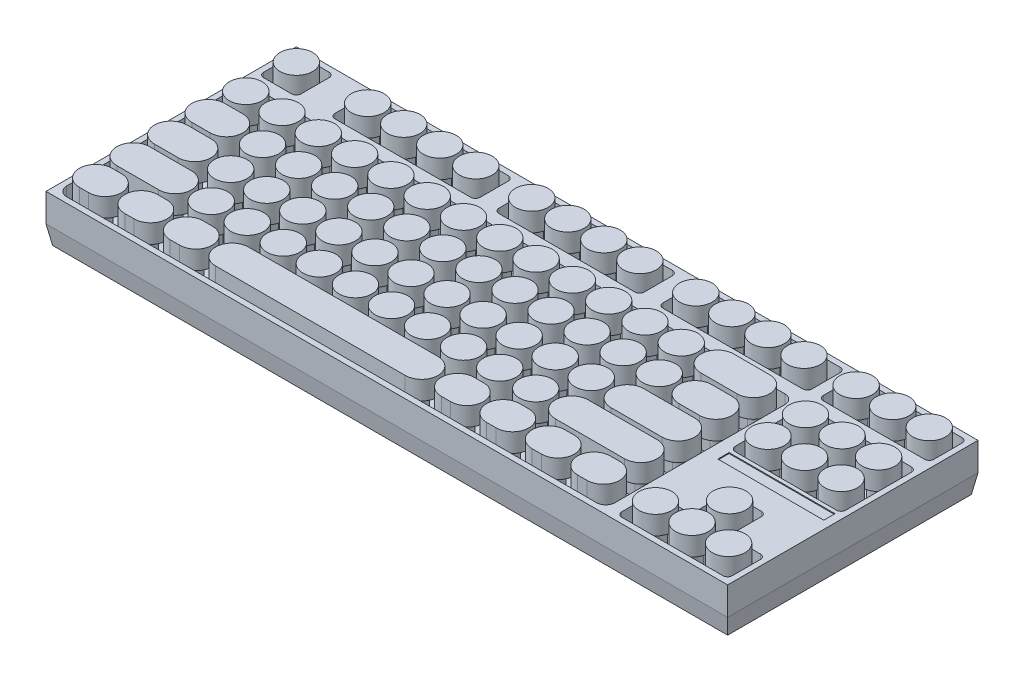
SolidWorks part; units mm, degrees
ref_plane "Front Plane" through (0, 0, 0) normal (0, 0, 1) x (1, 0, 0)
ref_plane "Top Plane" through (0, 0, 0) normal (0, 1, 0) x (1, 0, 0)
ref_plane "Right Plane" through (0, 0, 0) normal (1, 0, 0) x (0, 0, -1)
sketch "Sketch1" plane through (0, 0, 0) normal (0, 1, 0) x (1, 0, 0)
  line L1 (180, 65) -> (-180, 65)
  line L2 (180, 65) -> (180, -65)
  line L3 (180, -65) -> (-180, -65)
  line L4 (-180, 65) -> (-180, -65)
  line L5 (180, 65) -> (-180, -65) construction
  line L6 (180, -65) -> (-180, 65) construction
  point P0 (0, 0)
  dimension "D1" = 360
  dimension "D2" = 130
extrude "Boss-Extrude1" add sketch "Sketch1" along normal blind 10
draft "Draft1" type of draft neutral plane draft angle 10 faces to draft 4 face at (180, 5, 0) face at (0, 5, -65) face at (-180, 5, 0) face at (0, 5, 65) neutral plane through (0, 0, 0) neutral plane normal (0, -1, 0) parameters "D1"=10
sketch "Sketch2" plane through (0, 10, 0) normal (0, 1, 0) x (1, 0, 0)
  line L0 (111.2633, 63.7633) -> (36.7667, 63.7633)
  line L1 (113.7633, 61.2633) -> (113.7633, 46.2633)
  line L2 (111.2633, 43.7633) -> (36.7667, 43.7633)
  line L3 (34.2667, 61.2633) -> (34.2667, 46.2633)
  line L4 (176.2633, 63.7633) -> (122.2633, 63.7633)
  line L5 (176.2633, -43.7633) -> (122.2633, -43.7633) construction
  line L6 (178.7633, -46.2633) -> (178.7633, -61.2633)
  line L7 (176.2633, -63.7633) -> (122.2633, -63.7633)
  line L8 (119.7633, -46.2633) -> (119.7633, -61.2633)
  line L9 (178.7633, -43.7633) -> (119.7633, -63.7633) construction
  line L10 (178.7633, -63.7633) -> (119.7633, -43.7633) construction
  line L11 (156.7633, -23.7633) -> (141.7633, -23.7633)
  line L12 (159.2633, -26.2633) -> (159.2633, -41.2633)
  line L13 (159.2633, -43.7633) -> (139.2633, -43.7633) construction
  line L14 (139.2633, -26.2633) -> (139.2633, -41.2633)
  line L15 (159.2633, -23.7633) -> (139.2633, -43.7633) construction
  line L16 (-178.7633, 66.7633) -> (-178.7633, -66.7633)
  line L17 (-178.7633, 31.7633) -> (-178.7633, -58.7633)
  line L18 (159.2633, -43.7633) -> (139.2633, -23.7633) construction
  line L19 (181.7633, 36.7633) -> (-181.7633, 36.7633)
  line L20 (108.7633, 36.7633) -> (-173.7633, 36.7633)
  line L21 (178.7633, 61.2633) -> (178.7633, 46.2633)
  line L22 (113.7633, -66.7633) -> (113.7633, 66.7633)
  line L23 (113.7633, -58.7633) -> (113.7633, 31.7633)
  line L24 (176.2633, 43.7633) -> (122.2633, 43.7633)
  line L25 (-181.7633, -63.7633) -> (181.7633, -63.7633)
  line L26 (-173.7633, -63.7633) -> (108.7633, -63.7633)
  line L27 (-181.7633, 66.7633) -> (-181.7633, -66.7633) construction
  line L28 (-161.2633, 63.7633) -> (-176.2633, 63.7633)
  line L29 (-158.7633, 61.2633) -> (-158.7633, 46.2633)
  line L30 (-161.2633, 43.7633) -> (-176.2633, 43.7633)
  line L31 (-178.7633, 61.2633) -> (-178.7633, 46.2633)
  line L32 (-158.7633, 63.7633) -> (-178.7633, 43.7633) construction
  line L33 (-158.7633, 43.7633) -> (-178.7633, 63.7633) construction
  line L34 (181.7633, 66.7633) -> (-181.7633, 66.7633) construction
  line L35 (-181.7633, -66.7633) -> (181.7633, -66.7633) construction
  line L36 (-65.7333, 63.7633) -> (-138.2333, 63.7633)
  line L37 (-63.2333, 61.2633) -> (-63.2333, 46.2633)
  line L38 (-65.7333, 43.7633) -> (-138.2333, 43.7633)
  line L39 (-140.7333, 61.2633) -> (-140.7333, 46.2633)
  line L40 (-63.2333, 63.7633) -> (-140.7333, 43.7633) construction
  line L41 (-63.2333, 43.7633) -> (-140.7333, 63.7633) construction
  line L42 (181.7633, -66.7633) -> (181.7633, 66.7633) construction
  line L43 (-181.7633, 66.7633) -> (-181.7633, -66.7633)
  line L44 (-181.7633, -66.7633) -> (181.7633, -66.7633)
  line L45 (181.7633, -66.7633) -> (181.7633, 66.7633)
  line L46 (181.7633, 66.7633) -> (-181.7633, 66.7633)
  line L47 (21.7667, 63.7633) -> (-50.7333, 63.7633)
  line L48 (24.2667, 61.2633) -> (24.2667, 46.2633)
  line L49 (21.7667, 43.7633) -> (-50.7333, 43.7633)
  line L50 (-53.2333, 61.2633) -> (-53.2333, 46.2633)
  line L51 (119.7633, 61.2633) -> (119.7633, 46.2633)
  line L52 (122.2633, -43.7633) -> (136.7633, -43.7633)
  line L53 (176.2633, 36.7633) -> (122.2633, 36.7633)
  line L54 (178.7633, 34.2633) -> (178.7633, -0.7367)
  line L55 (176.2633, -3.2367) -> (122.2633, -3.2367)
  line L56 (119.7633, 34.2633) -> (119.7633, -0.7367)
  line L57 (178.7633, 36.7633) -> (119.7633, -3.2367) construction
  line L58 (178.7633, -3.2367) -> (119.7633, 36.7633) construction
  line L59 (176.2633, -43.7633) -> (161.7633, -43.7633)
  arc A0 (108.7633, -63.7633) -> (113.7633, -58.7633) centre (108.7633, -58.7633) ccw
  arc A1 (113.7633, 31.7633) -> (108.7633, 36.7633) centre (108.7633, 31.7633) ccw
  arc A2 (-173.7633, -63.7633) -> (-178.7633, -58.7633) centre (-173.7633, -58.7633) cw
  arc A3 (-178.7633, 31.7633) -> (-173.7633, 36.7633) centre (-173.7633, 31.7633) cw
  arc A4 (178.7633, -61.2633) -> (176.2633, -63.7633) centre (176.2633, -61.2633) cw
  arc A5 (176.2633, -43.7633) -> (178.7633, -46.2633) centre (176.2633, -46.2633) cw
  arc A6 (122.2633, -43.7633) -> (119.7633, -46.2633) centre (122.2633, -46.2633) ccw
  arc A7 (122.2633, -63.7633) -> (119.7633, -61.2633) centre (122.2633, -61.2633) cw
  arc A8 (156.7633, -23.7633) -> (159.2633, -26.2633) centre (156.7633, -26.2633) cw
  arc A9 (141.7633, -23.7633) -> (139.2633, -26.2633) centre (141.7633, -26.2633) ccw
  arc A10 (178.7633, -0.7367) -> (176.2633, -3.2367) centre (176.2633, -0.7367) cw
  arc A11 (122.2633, -3.2367) -> (119.7633, -0.7367) centre (122.2633, -0.7367) cw
  arc A12 (122.2633, 36.7633) -> (119.7633, 34.2633) centre (122.2633, 34.2633) ccw
  arc A13 (176.2633, 36.7633) -> (178.7633, 34.2633) centre (176.2633, 34.2633) cw
  arc A14 (178.7633, 46.2633) -> (176.2633, 43.7633) centre (176.2633, 46.2633) cw
  arc A15 (176.2633, 63.7633) -> (178.7633, 61.2633) centre (176.2633, 61.2633) cw
  arc A16 (122.2633, 63.7633) -> (119.7633, 61.2633) centre (122.2633, 61.2633) ccw
  arc A17 (122.2633, 43.7633) -> (119.7633, 46.2633) centre (122.2633, 46.2633) cw
  arc A18 (113.7633, 46.2633) -> (111.2633, 43.7633) centre (111.2633, 46.2633) cw
  arc A19 (111.2633, 63.7633) -> (113.7633, 61.2633) centre (111.2633, 61.2633) cw
  arc A20 (36.7667, 63.7633) -> (34.2667, 61.2633) centre (36.7667, 61.2633) ccw
  arc A21 (36.7667, 43.7633) -> (34.2667, 46.2633) centre (36.7667, 46.2633) cw
  arc A22 (24.2667, 46.2633) -> (21.7667, 43.7633) centre (21.7667, 46.2633) cw
  arc A23 (21.7667, 63.7633) -> (24.2667, 61.2633) centre (21.7667, 61.2633) cw
  arc A24 (-50.7333, 43.7633) -> (-53.2333, 46.2633) centre (-50.7333, 46.2633) cw
  arc A25 (-50.7333, 63.7633) -> (-53.2333, 61.2633) centre (-50.7333, 61.2633) ccw
  arc A26 (-63.2333, 46.2633) -> (-65.7333, 43.7633) centre (-65.7333, 46.2633) cw
  arc A27 (-65.7333, 63.7633) -> (-63.2333, 61.2633) centre (-65.7333, 61.2633) cw
  arc A28 (-138.2333, 43.7633) -> (-140.7333, 46.2633) centre (-138.2333, 46.2633) cw
  arc A29 (-138.2333, 63.7633) -> (-140.7333, 61.2633) centre (-138.2333, 61.2633) ccw
  arc A30 (-158.7633, 46.2633) -> (-161.2633, 43.7633) centre (-161.2633, 46.2633) cw
  arc A31 (-176.2633, 43.7633) -> (-178.7633, 46.2633) centre (-176.2633, 46.2633) cw
  arc A32 (-176.2633, 63.7633) -> (-178.7633, 61.2633) centre (-176.2633, 61.2633) ccw
  arc A33 (-161.2633, 63.7633) -> (-158.7633, 61.2633) centre (-161.2633, 61.2633) cw
  arc A34 (136.7633, -43.7633) -> (139.2633, -41.2633) centre (136.7633, -41.2633) ccw
  arc A35 (159.2633, -41.2633) -> (161.7633, -43.7633) centre (161.7633, -41.2633) ccw
  point P22 (-168.7633, 53.7633)
  point P30 (-101.9833, 53.7633)
  point P42 (149.2633, -53.7633)
  point P47 (149.2633, -33.7633)
  point P57 (149.2633, 16.7633)
  point P94 (178.7633, 43.7633)
  point P97 (178.7633, 63.7633)
  point P104 (113.7633, 43.7633)
  point P107 (113.7633, 63.7633)
  point P110 (34.2667, 63.7633)
  point P115 (24.2667, 43.7633)
  point P118 (24.2667, 63.7633)
  point P123 (-53.2333, 63.7633)
  point P153 (0, 0)
  dimension "D5" = 5
  dimension "D34" = 2.5
  dimension "D35" = 2.5
  dimension "D6" = 20
  dimension "D7" = 3
  dimension "D8" = 3
  dimension "D9" = 18.03
  dimension "D10" = 77.5
  dimension "D11" = 20
  dimension "D12" = 3
  dimension "D13" = 10
  dimension "D14" = 3
  dimension "D15" = 20
  dimension "D16" = 77.5
  dimension "D18" = 20
  dimension "D19" = 3
  dimension "D20" = 10
  dimension "D21" = 3
  dimension "D22" = 6
  dimension "D23" = 3
  dimension "D24" = 20
  dimension "D25" = 20
  dimension "D26" = 20
  dimension "D28" = 20
  dimension "D29" = 3
  dimension "D30" = 3
  dimension "D31" = 40
  dimension "D32" = 3
  dimension "D33" = 6
  dimension "D1" = 3
  dimension "D2" = 30
  dimension "D3" = 68
  dimension "D4" = 3
extrude "Boss-Extrude2" add sketch "Sketch2" along normal blind 15
sketch "Sketch3" plane through (0, 10, 0) normal (0, 1, 0) x (1, 0, 0)
  line L0 (-178.031, 63.031) -> (-159.4955, 44.4955) construction
  line L1 (-178.031, 44.4955) -> (-159.4955, 63.031) construction
  line L2 (178.7633, 46.2633) -> (178.7633, 61.2633) construction
  line L3 (-63.2333, 46.2633) -> (-63.2333, 61.2633) construction
  line L4 (176.2633, 36.7633) -> (122.2633, 36.7633) construction
  line L5 (-140.7333, 61.2633) -> (-140.7333, 46.2633) construction
  line L6 (178.7633, 16.7633) -> (119.7633, 16.7633) construction
  line L7 (178.7633, -0.7367) -> (178.7633, 34.2633) construction
  line L8 (119.7633, 34.2633) -> (119.7633, -0.7367) construction
  line L9 (90.9667, 6.7633) -> (101.9567, 6.7633) construction
  line L10 (-168.7633, 6.7633) -> (-159.0233, 6.7633) construction
  line L11 (-168.7633, 9.7633) -> (-159.0233, 9.7633)
  line L12 (-168.7633, 3.7633) -> (-159.0233, 3.7633)
  line L13 (-168.7633, -13.2367) -> (-156.0233, -13.2367) construction
  line L14 (-53.2333, 61.2633) -> (-53.2333, 46.2633) construction
  line L15 (34.2667, 61.2633) -> (34.2667, 46.2633) construction
  line L16 (119.7633, 61.2633) -> (119.7633, 46.2633) construction
  line L17 (-168.7633, -10.2367) -> (-156.0233, -10.2367)
  line L18 (-168.7633, -16.2367) -> (-156.0233, -16.2367)
  line L19 (-168.7633, -33.2367) -> (-146.4083, -33.2367) construction
  line L20 (-168.7633, -30.2367) -> (-146.4083, -30.2367)
  line L21 (-168.7633, -36.2367) -> (-146.4083, -36.2367)
  line L22 (82.7267, 26.7633) -> (101.9567, 26.7633) construction
  line L23 (82.7267, 29.7633) -> (101.9567, 29.7633)
  line L24 (82.7267, 23.7633) -> (101.9567, 23.7633)
  line L25 (90.9667, 9.7633) -> (101.9567, 9.7633)
  line L26 (90.9667, 3.7633) -> (101.9567, 3.7633)
  line L27 (74.7367, -13.2367) -> (101.9567, -13.2367) construction
  line L28 (74.7367, -10.2367) -> (101.9567, -10.2367)
  line L29 (74.7367, -16.2367) -> (101.9567, -16.2367)
  line L30 (65.1217, -33.2367) -> (101.9567, -33.2367) construction
  line L31 (65.1217, -30.2367) -> (101.9567, -30.2367)
  line L32 (65.1217, -36.2367) -> (101.9567, -36.2367)
  line L33 (-168.7633, -53.2367) -> (-163.7633, -53.2367) construction
  line L34 (-168.7633, -50.2367) -> (-163.7633, -50.2367)
  line L35 (-168.7633, -56.2367) -> (-163.7633, -56.2367)
  line L36 (-144.5333, -53.2367) -> (-139.5333, -53.2367) construction
  line L37 (-144.5333, -50.2367) -> (-139.5333, -50.2367)
  line L38 (-144.5333, -56.2367) -> (-139.5333, -56.2367)
  line L39 (-120.3033, -53.2367) -> (-115.3033, -53.2367) construction
  line L40 (-120.3033, -50.2367) -> (-115.3033, -50.2367)
  line L41 (-120.3033, -56.2367) -> (-115.3033, -56.2367)
  line L42 (96.9567, -53.2367) -> (101.9567, -53.2367) construction
  line L43 (96.9567, -50.2367) -> (101.9567, -50.2367)
  line L44 (96.9567, -56.2367) -> (101.9567, -56.2367)
  line L45 (72.7267, -50.2367) -> (77.7267, -50.2367)
  line L46 (72.7267, -56.2367) -> (77.7267, -56.2367)
  line L47 (72.7267, -53.2367) -> (77.7267, -53.2367) construction
  line L48 (48.4967, -50.2367) -> (53.4967, -50.2367)
  line L49 (48.4967, -56.2367) -> (53.4967, -56.2367)
  line L50 (48.4967, -53.2367) -> (53.4967, -53.2367) construction
  line L51 (24.2667, -50.2367) -> (29.2667, -50.2367)
  line L52 (24.2667, -56.2367) -> (29.2667, -56.2367)
  line L53 (24.2667, -53.2367) -> (29.2667, -53.2367) construction
  line L54 (-96.0733, -53.2367) -> (5.0367, -53.2367) construction
  line L55 (-96.0733, -50.2367) -> (5.0367, -50.2367)
  line L56 (-96.0733, -56.2367) -> (5.0367, -56.2367)
  arc A0 (-176.2633, 63.7633) -> (-178.7633, 61.2633) centre (-176.2633, 61.2633) ccw construction
  arc A1 (-161.2633, 43.7633) -> (-158.7633, 46.2633) centre (-161.2633, 46.2633) ccw construction
  arc A2 (-178.7633, 46.2633) -> (-176.2633, 43.7633) centre (-176.2633, 46.2633) ccw construction
  arc A3 (-158.7633, 61.2633) -> (-161.2633, 63.7633) centre (-161.2633, 61.2633) ccw construction
  circle A4 centre (-168.7633, 53.7633) radius 4.5
  circle A5 centre (-130.7333, 53.7633) radius 4.5
  circle A6 centre (-111.5083, 53.7633) radius 4.5
  circle A7 centre (-92.4583, 53.7633) radius 4.5
  circle A8 centre (-73.2333, 53.7633) radius 4.5
  circle A43 centre (-43.2333, 53.7633) radius 4.5
  circle A44 centre (44.2667, 53.7633) radius 4.5
  circle A45 centre (129.7633, 53.7633) radius 4.5
  circle A46 centre (-24.0033, 53.7633) radius 4.5
  circle A47 centre (-4.7733, 53.7633) radius 4.5
  circle A48 centre (14.4567, 53.7633) radius 4.5
  circle A49 centre (63.4967, 53.7633) radius 4.5
  circle A50 centre (82.7267, 53.7633) radius 4.5
  circle A51 centre (101.9567, 53.7633) radius 4.5
  circle A52 centre (168.7633, 53.7633) radius 4.5
  circle A53 centre (149.2633, 53.7633) radius 4.5
  circle A54 centre (129.7633, 26.7633) radius 4.5
  circle A55 centre (149.2633, 26.7633) radius 4.5
  circle A56 centre (168.7633, 26.7633) radius 4.5
  circle A57 centre (168.7633, 6.7633) radius 4.5
  circle A58 centre (149.2633, 6.7633) radius 4.5
  circle A59 centre (129.7633, 6.7633) radius 4.5
  circle A60 centre (63.4967, 26.7633) radius 4.5
  circle A61 centre (44.1417, 26.7633) radius 4.5
  circle A62 centre (24.7867, 26.7633) radius 4.5
  circle A63 centre (5.4317, 26.7633) radius 4.5
  circle A64 centre (-13.9233, 26.7633) radius 4.5
  circle A65 centre (-33.2783, 26.7633) radius 4.5
  circle A66 centre (-52.6333, 26.7633) radius 4.5
  circle A67 centre (-71.9883, 26.7633) radius 4.5
  circle A68 centre (-91.3433, 26.7633) radius 4.5
  circle A69 centre (-110.6983, 26.7633) radius 4.5
  circle A70 centre (-130.0533, 26.7633) radius 4.5
  circle A71 centre (-149.4083, 26.7633) radius 4.5
  circle A72 centre (-168.7633, 26.7633) radius 4.5
  circle A73 centre (129.7633, -53.2367) radius 4.5
  circle A74 centre (149.2633, -53.2367) radius 4.5
  circle A75 centre (168.7633, -53.2367) radius 4.5
  circle A76 centre (149.2633, -33.2367) radius 4.5
  circle A78 centre (-139.7933, 6.7633) radius 4.5
  circle A90 centre (-120.5633, 6.7633) radius 4.5
  circle A91 centre (-101.3333, 6.7633) radius 4.5
  circle A92 centre (-82.1033, 6.7633) radius 4.5
  circle A93 centre (-62.8733, 6.7633) radius 4.5
  circle A94 centre (-43.6433, 6.7633) radius 4.5
  circle A95 centre (-24.4133, 6.7633) radius 4.5
  circle A96 centre (-5.1833, 6.7633) radius 4.5
  circle A97 centre (14.0467, 6.7633) radius 4.5
  circle A98 centre (33.2767, 6.7633) radius 4.5
  circle A99 centre (52.5067, 6.7633) radius 4.5
  circle A100 centre (71.7367, 6.7633) radius 4.5
  circle A101 centre (-136.7933, -13.2367) radius 4.5
  circle A102 centre (-117.5633, -13.2367) radius 4.5
  circle A103 centre (-98.3333, -13.2367) radius 4.5
  circle A104 centre (-79.1033, -13.2367) radius 4.5
  circle A105 centre (-59.8733, -13.2367) radius 4.5
  circle A106 centre (-40.6433, -13.2367) radius 4.5
  circle A107 centre (-21.4133, -13.2367) radius 4.5
  circle A108 centre (-2.1833, -13.2367) radius 4.5
  circle A109 centre (17.0467, -13.2367) radius 4.5
  circle A110 centre (36.2767, -13.2367) radius 4.5
  circle A111 centre (55.5067, -13.2367) radius 4.5
  circle A112 centre (-127.1783, -33.2367) radius 4.5
  circle A113 centre (-107.9483, -33.2367) radius 4.5
  circle A114 centre (-88.7183, -33.2367) radius 4.5
  circle A115 centre (-69.4883, -33.2367) radius 4.5
  circle A116 centre (-50.2583, -33.2367) radius 4.5
  circle A117 centre (-31.0283, -33.2367) radius 4.5
  circle A118 centre (-11.7983, -33.2367) radius 4.5
  circle A119 centre (7.4317, -33.2367) radius 4.5
  circle A120 centre (26.6617, -33.2367) radius 4.5
  circle A121 centre (45.8917, -33.2367) radius 4.5
  arc A122 (-168.7633, 9.7633) -> (-168.7633, 3.7633) centre (-168.7633, 6.7633) ccw
  arc A123 (-159.0233, 3.7633) -> (-159.0233, 9.7633) centre (-159.0233, 6.7633) ccw
  arc A124 (-168.7633, -10.2367) -> (-168.7633, -16.2367) centre (-168.7633, -13.2367) ccw
  arc A125 (-156.0233, -16.2367) -> (-156.0233, -10.2367) centre (-156.0233, -13.2367) ccw
  arc A126 (-168.7633, -30.2367) -> (-168.7633, -36.2367) centre (-168.7633, -33.2367) ccw
  arc A127 (-146.4083, -36.2367) -> (-146.4083, -30.2367) centre (-146.4083, -33.2367) ccw
  arc A128 (82.7267, 29.7633) -> (82.7267, 23.7633) centre (82.7267, 26.7633) ccw
  arc A129 (101.9567, 23.7633) -> (101.9567, 29.7633) centre (101.9567, 26.7633) ccw
  arc A130 (90.9667, 9.7633) -> (90.9667, 3.7633) centre (90.9667, 6.7633) ccw
  arc A131 (101.9567, 3.7633) -> (101.9567, 9.7633) centre (101.9567, 6.7633) ccw
  arc A132 (74.7367, -10.2367) -> (74.7367, -16.2367) centre (74.7367, -13.2367) ccw
  arc A133 (101.9567, -16.2367) -> (101.9567, -10.2367) centre (101.9567, -13.2367) ccw
  arc A134 (65.1217, -30.2367) -> (65.1217, -36.2367) centre (65.1217, -33.2367) ccw
  arc A135 (101.9567, -36.2367) -> (101.9567, -30.2367) centre (101.9567, -33.2367) ccw
  arc A136 (-168.7633, -50.2367) -> (-168.7633, -56.2367) centre (-168.7633, -53.2367) ccw
  arc A137 (-163.7633, -56.2367) -> (-163.7633, -50.2367) centre (-163.7633, -53.2367) ccw
  arc A138 (-144.5333, -50.2367) -> (-144.5333, -56.2367) centre (-144.5333, -53.2367) ccw
  arc A139 (-139.5333, -56.2367) -> (-139.5333, -50.2367) centre (-139.5333, -53.2367) ccw
  arc A140 (-120.3033, -50.2367) -> (-120.3033, -56.2367) centre (-120.3033, -53.2367) ccw
  arc A141 (-115.3033, -56.2367) -> (-115.3033, -50.2367) centre (-115.3033, -53.2367) ccw
  arc A142 (96.9567, -50.2367) -> (96.9567, -56.2367) centre (96.9567, -53.2367) ccw
  arc A143 (101.9567, -56.2367) -> (101.9567, -50.2367) centre (101.9567, -53.2367) ccw
  arc A144 (77.7267, -56.2367) -> (77.7267, -50.2367) centre (77.7267, -53.2367) ccw
  arc A145 (72.7267, -50.2367) -> (72.7267, -56.2367) centre (72.7267, -53.2367) ccw
  arc A146 (53.4967, -56.2367) -> (53.4967, -50.2367) centre (53.4967, -53.2367) ccw
  arc A147 (48.4967, -50.2367) -> (48.4967, -56.2367) centre (48.4967, -53.2367) ccw
  arc A148 (29.2667, -56.2367) -> (29.2667, -50.2367) centre (29.2667, -53.2367) ccw
  arc A149 (24.2667, -50.2367) -> (24.2667, -56.2367) centre (24.2667, -53.2367) ccw
  arc A150 (-96.0733, -50.2367) -> (-96.0733, -56.2367) centre (-96.0733, -53.2367) ccw
  arc A151 (5.0367, -56.2367) -> (5.0367, -50.2367) centre (5.0367, -53.2367) ccw
  point P113 (-163.8933, 6.7633)
  point P187 (-162.3933, -13.2367)
  point P194 (-166.2633, -53.2367)
  point P196 (-157.5858, -33.2367)
  point P203 (92.3417, 26.7633)
  point P212 (96.4617, 6.7633)
  point P220 (88.3467, -13.2367)
  point P227 (-142.0333, -53.2367)
  point P228 (99.4567, -53.2367)
  point P229 (83.5392, -33.2367)
  point P244 (-117.8033, -53.2367)
  point P257 (75.2267, -53.2367)
  point P265 (50.9967, -53.2367)
  point P272 (26.7667, -53.2367)
  point P280 (-45.5183, -53.2367)
  dimension "D1" = 9
  dimension "D30" = 3
  dimension "D34" = 3
  dimension "D35" = 3
  dimension "D37" = 3
  dimension "D39" = 3
  dimension "D41" = 3
  dimension "D43" = 3
  dimension "D44" = 3
  dimension "D46" = 3
  dimension "D48" = 3
  dimension "D51" = 3
  dimension "D2" = 10
  dimension "D3" = 10
  dimension "D4" = 19.225
  dimension "D5" = 19.225
  dimension "D6" = 10
  dimension "D7" = 10
  dimension "D8" = 10
  dimension "D9" = 19.23
  dimension "D10" = 19.23
  dimension "D11" = 10
  dimension "D12" = 19.5
  dimension "D13" = 10
  dimension "D14" = 19.5
  dimension "D15" = 3
  dimension "D16" = 4
  dimension "D17" = 20
  dimension "D18" = 10
  dimension "D19" = 3
  dimension "D20" = 13
  dimension "D21" = 20
  dimension "D22" = 9.615
  dimension "D23" = 19.23
  dimension "D24" = 12
  dimension "D26" = 3
  dimension "D25" = 20
  dimension "D27" = 19.23
  dimension "D29" = 9.615
  dimension "D31" = 9.615
  dimension "D32" = 19.23
  dimension "D33" = 19.23
  dimension "D36" = 19.23
  dimension "D38" = 19.23
  dimension "D40" = 19.23
  dimension "D42" = 19.23
  dimension "D45" = 5
  dimension "D47" = 19.23
  dimension "D49" = 5
  dimension "D50" = 19.23
  dimension "D52" = 19.23
  dimension "D53" = 19.23
  dimension "D28" = 11
extrude "Boss-Extrude3" add sketch "Sketch3" along normal blind 15
sketch "Sketch4" plane through (0, 25, 0) normal (0, 1, 0) x (1, 0, 0)
  line L0 (-168.7633, 6.7633) -> (-159.0233, 6.7633) construction
  line L3 (-168.7633, 15.5133) -> (-159.0233, 15.5133)
  line L4 (-168.7633, -1.9867) -> (-159.0233, -1.9867)
  line L5 (-168.7633, -13.2367) -> (-156.0233, -13.2367) construction
  line L6 (-168.7633, -4.4867) -> (-156.0233, -4.4867)
  line L7 (-168.7633, -21.9867) -> (-156.0233, -21.9867)
  line L8 (-168.7633, -33.2367) -> (-146.4083, -33.2367) construction
  line L9 (-168.7633, -24.4867) -> (-146.4083, -24.4867)
  line L10 (-168.7633, -41.9867) -> (-146.4083, -41.9867)
  line L11 (82.7267, 26.7633) -> (101.9567, 26.7633) construction
  line L12 (82.7267, 35.5133) -> (101.9567, 35.5133)
  line L13 (82.7267, 18.0133) -> (101.9567, 18.0133)
  line L14 (90.9667, 6.7633) -> (101.9567, 6.7633) construction
  line L15 (90.9667, 15.5133) -> (101.9567, 15.5133)
  line L16 (90.9667, -1.9867) -> (101.9567, -1.9867)
  line L17 (74.7367, -13.2367) -> (101.9567, -13.2367) construction
  line L18 (74.7367, -4.4867) -> (101.9567, -4.4867)
  line L19 (74.7367, -21.9867) -> (101.9567, -21.9867)
  line L20 (65.1217, -33.2367) -> (101.9567, -33.2367) construction
  line L21 (65.1217, -24.4867) -> (101.9567, -24.4867)
  line L22 (65.1217, -41.9867) -> (101.9567, -41.9867)
  line L23 (-168.7633, -53.2367) -> (-163.7633, -53.2367) construction
  line L24 (-168.7633, -44.4867) -> (-163.7633, -44.4867)
  line L25 (-168.7633, -61.9867) -> (-163.7633, -61.9867)
  line L26 (-144.5333, -61.9867) -> (-139.5333, -61.9867)
  line L29 (-144.5333, -44.4867) -> (-139.5333, -44.4867)
  line L30 (-144.5333, -53.2367) -> (-139.5333, -53.2367) construction
  line L31 (-120.3033, -61.9867) -> (-115.3033, -61.9867)
  line L32 (-120.3033, -44.4867) -> (-115.3033, -44.4867)
  line L33 (-120.3033, -53.2367) -> (-115.3033, -53.2367) construction
  line L34 (96.9567, -61.9867) -> (101.9567, -61.9867)
  line L35 (96.9567, -44.4867) -> (101.9567, -44.4867)
  line L36 (96.9567, -53.2367) -> (101.9567, -53.2367) construction
  line L37 (72.7267, -44.4867) -> (77.7267, -44.4867)
  line L38 (72.7267, -61.9867) -> (77.7267, -61.9867)
  line L39 (72.7267, -53.2367) -> (77.7267, -53.2367) construction
  line L40 (48.4967, -44.4867) -> (53.4967, -44.4867)
  line L41 (48.4967, -61.9867) -> (53.4967, -61.9867)
  line L42 (48.4967, -53.2367) -> (53.4967, -53.2367) construction
  line L43 (24.2667, -44.4867) -> (29.2667, -44.4867)
  line L44 (24.2667, -61.9867) -> (29.2667, -61.9867)
  line L45 (24.2667, -53.2367) -> (29.2667, -53.2367) construction
  line L46 (-96.0733, -53.2367) -> (5.0367, -53.2367) construction
  line L47 (-96.0733, -44.4867) -> (5.0367, -44.4867)
  line L48 (-96.0733, -61.9867) -> (5.0367, -61.9867)
  circle A0 centre (-168.7633, 53.7633) radius 8.75
  circle A1 centre (-130.7333, 53.7633) radius 8.75
  circle A2 centre (-111.5083, 53.7633) radius 8.75
  circle A3 centre (-92.2833, 53.7633) radius 8.75
  circle A4 centre (-73.0583, 53.7633) radius 8.75
  circle A5 centre (-43.2333, 53.7633) radius 8.75
  circle A6 centre (-24.0033, 53.7633) radius 8.75
  circle A7 centre (-4.7733, 53.7633) radius 8.75
  circle A8 centre (14.4567, 53.7633) radius 8.75
  circle A9 centre (44.2667, 53.7633) radius 8.75
  circle A10 centre (63.4967, 53.7633) radius 8.75
  circle A11 centre (82.7267, 53.7633) radius 8.75
  circle A12 centre (101.9567, 53.7633) radius 8.75
  circle A13 centre (129.7633, 53.7633) radius 8.75
  circle A16 centre (149.2633, 53.7633) radius 8.75
  circle A17 centre (168.7633, 53.7633) radius 8.75
  circle A18 centre (63.4967, 26.7633) radius 8.75
  circle A19 centre (44.1417, 26.7633) radius 8.75
  circle A20 centre (24.7867, 26.7633) radius 8.75
  circle A21 centre (5.4317, 26.7633) radius 8.75
  circle A22 centre (-13.9233, 26.7633) radius 8.75
  circle A23 centre (-33.2783, 26.7633) radius 8.75
  circle A24 centre (-52.6333, 26.7633) radius 8.75
  circle A25 centre (-71.9883, 26.7633) radius 8.75
  circle A26 centre (-91.3433, 26.7633) radius 8.75
  circle A27 centre (-110.6983, 26.7633) radius 8.75
  circle A28 centre (-130.0533, 26.7633) radius 8.75
  circle A29 centre (-149.4083, 26.7633) radius 8.75
  circle A30 centre (-168.7633, 26.7633) radius 8.75
  circle A31 centre (71.7367, 6.7633) radius 8.75
  circle A32 centre (52.5067, 6.7633) radius 8.75
  circle A33 centre (33.2767, 6.7633) radius 8.75
  circle A34 centre (14.0467, 6.7633) radius 8.75
  circle A35 centre (-5.1833, 6.7633) radius 8.75
  circle A36 centre (-24.4133, 6.7633) radius 8.75
  circle A37 centre (-43.6433, 6.7633) radius 8.75
  circle A38 centre (-62.8733, 6.7633) radius 8.75
  circle A39 centre (-82.1033, 6.7633) radius 8.75
  circle A40 centre (-101.3333, 6.7633) radius 8.75
  circle A41 centre (-120.5633, 6.7633) radius 8.75
  circle A42 centre (-139.7933, 6.7633) radius 8.75
  circle A44 centre (129.7633, 26.7633) radius 8.75
  circle A45 centre (129.7633, 6.7633) radius 8.75
  circle A48 centre (168.7633, 26.7633) radius 8.75
  circle A49 centre (168.7633, 6.7633) radius 8.75
  circle A50 centre (149.2633, 26.7633) radius 8.75 [skipped]
  circle A51 centre (149.2633, 6.7633) radius 8.75 [skipped]
  circle A52 centre (149.2633, 26.7633) radius 8.75
  circle A53 centre (149.2633, 6.7633) radius 8.75
  circle A54 centre (-159.0233, 6.7633) radius 8.75 [skipped]
  circle A55 centre (129.7633, -53.2367) radius 8.75
  circle A56 centre (149.2633, -33.2367) radius 8.75
  circle A57 centre (149.2633, -53.2367) radius 8.75
  circle A58 centre (168.7633, -53.2367) radius 8.75
  circle A59 centre (-136.7933, -13.2367) radius 8.75
  circle A60 centre (-117.5633, -13.2367) radius 8.75
  circle A61 centre (-98.3333, -13.2367) radius 8.75
  circle A62 centre (-79.1033, -13.2367) radius 8.75
  circle A63 centre (-59.8733, -13.2367) radius 8.75
  circle A64 centre (-40.6433, -13.2367) radius 8.75
  circle A65 centre (-21.4133, -13.2367) radius 8.75
  circle A66 centre (-2.1833, -13.2367) radius 8.75
  circle A67 centre (17.0467, -13.2367) radius 8.75
  circle A68 centre (36.2767, -13.2367) radius 8.75
  circle A69 centre (55.5067, -13.2367) radius 8.75
  circle A70 centre (-127.1783, -33.2367) radius 8.75
  circle A71 centre (-107.9483, -33.2367) radius 8.75
  circle A72 centre (-88.7183, -33.2367) radius 8.75
  circle A73 centre (-69.4883, -33.2367) radius 8.75
  circle A74 centre (-50.2583, -33.2367) radius 8.75
  circle A75 centre (-31.0283, -33.2367) radius 8.75
  circle A76 centre (-11.7983, -33.2367) radius 8.75
  circle A77 centre (7.4317, -33.2367) radius 8.75
  circle A78 centre (26.6617, -33.2367) radius 8.75
  circle A79 centre (45.8917, -33.2367) radius 8.75
  arc A82 (-168.7633, 15.5133) -> (-168.7633, -1.9867) centre (-168.7633, 6.7633) ccw
  arc A83 (-159.0233, -1.9867) -> (-159.0233, 15.5133) centre (-159.0233, 6.7633) ccw
  arc A84 (-168.7633, -4.4867) -> (-168.7633, -21.9867) centre (-168.7633, -13.2367) ccw
  arc A85 (-156.0233, -21.9867) -> (-156.0233, -4.4867) centre (-156.0233, -13.2367) ccw
  arc A86 (-168.7633, -24.4867) -> (-168.7633, -41.9867) centre (-168.7633, -33.2367) ccw
  arc A87 (-146.4083, -41.9867) -> (-146.4083, -24.4867) centre (-146.4083, -33.2367) ccw
  arc A88 (82.7267, 35.5133) -> (82.7267, 18.0133) centre (82.7267, 26.7633) ccw
  arc A89 (101.9567, 18.0133) -> (101.9567, 35.5133) centre (101.9567, 26.7633) ccw
  arc A90 (90.9667, 15.5133) -> (90.9667, -1.9867) centre (90.9667, 6.7633) ccw
  arc A91 (101.9567, -1.9867) -> (101.9567, 15.5133) centre (101.9567, 6.7633) ccw
  arc A92 (74.7367, -4.4867) -> (74.7367, -21.9867) centre (74.7367, -13.2367) ccw
  arc A93 (101.9567, -21.9867) -> (101.9567, -4.4867) centre (101.9567, -13.2367) ccw
  arc A94 (65.1217, -24.4867) -> (65.1217, -41.9867) centre (65.1217, -33.2367) ccw
  arc A95 (101.9567, -41.9867) -> (101.9567, -24.4867) centre (101.9567, -33.2367) ccw
  arc A96 (-168.7633, -44.4867) -> (-168.7633, -61.9867) centre (-168.7633, -53.2367) ccw
  arc A97 (-163.7633, -61.9867) -> (-163.7633, -44.4867) centre (-163.7633, -53.2367) ccw
  arc A100 (-144.5333, -44.4867) -> (-144.5333, -61.9867) centre (-144.5333, -53.2367) ccw
  arc A101 (-139.5333, -61.9867) -> (-139.5333, -44.4867) centre (-139.5333, -53.2367) ccw
  arc A102 (-120.3033, -44.4867) -> (-120.3033, -61.9867) centre (-120.3033, -53.2367) ccw
  arc A103 (-115.3033, -61.9867) -> (-115.3033, -44.4867) centre (-115.3033, -53.2367) ccw
  arc A104 (96.9567, -44.4867) -> (96.9567, -61.9867) centre (96.9567, -53.2367) ccw
  arc A105 (101.9567, -61.9867) -> (101.9567, -44.4867) centre (101.9567, -53.2367) ccw
  arc A106 (77.7267, -61.9867) -> (77.7267, -44.4867) centre (77.7267, -53.2367) ccw
  arc A107 (72.7267, -44.4867) -> (72.7267, -61.9867) centre (72.7267, -53.2367) ccw
  arc A108 (53.4967, -61.9867) -> (53.4967, -44.4867) centre (53.4967, -53.2367) ccw
  arc A109 (48.4967, -44.4867) -> (48.4967, -61.9867) centre (48.4967, -53.2367) ccw
  arc A110 (29.2667, -61.9867) -> (29.2667, -44.4867) centre (29.2667, -53.2367) ccw
  arc A111 (24.2667, -44.4867) -> (24.2667, -61.9867) centre (24.2667, -53.2367) ccw
  arc A112 (-96.0733, -44.4867) -> (-96.0733, -61.9867) centre (-96.0733, -53.2367) ccw
  arc A113 (5.0367, -61.9867) -> (5.0367, -44.4867) centre (5.0367, -53.2367) ccw
  point P99 (-163.8933, 6.7633)
  point P185 (-162.3933, -13.2367)
  point P198 (-157.5858, -33.2367)
  point P207 (92.3417, 26.7633)
  point P212 (96.4617, 6.7633)
  point P221 (88.3467, -13.2367)
  point P230 (83.5392, -33.2367)
  point P243 (-166.2633, -53.2367)
  point P253 (-142.0333, -53.2367)
  point P260 (-117.8033, -53.2367)
  point P268 (99.4567, -53.2367)
  point P275 (75.2267, -53.2367)
  point P279 (-45.5183, -53.2367)
  point P284 (50.9967, -53.2367)
  point P291 (26.7667, -53.2367)
  dimension "D1" = 17.5
  dimension "D2" = 17.5
  dimension "D11" = 8.75
  dimension "D12" = 8.75
  dimension "D13" = 8.75
  dimension "D14" = 8.75
  dimension "D15" = 8.75
  dimension "D16" = 8.75
  dimension "D17" = 8.75
  dimension "D18" = 8.75
  dimension "D19" = 3
  dimension "D20" = 8.75
  dimension "D21" = 8.75
  dimension "D3" = 4
  dimension "D4" = 4
  dimension "D5" = 4
  dimension "D7" = 3
  dimension "D6" = 13
  dimension "D9" = 13
  dimension "D8" = 3
  dimension "D10" = 11
extrude "Boss-Extrude5" add sketch "Sketch4" along normal blind 10 from offset 4 offset against normal yes
sketch "Sketch5" plane through (0, 25, 0) normal (0, 1, 0) x (1, 0, 0)
  line L0 (121.0133, 6.7633) -> (121.0133, -11.2367) construction
  line L1 (121.0133, -5.2367) -> (177.5133, -5.2367)
  line L2 (121.0133, -5.2367) -> (121.0133, -11.2367)
  line L3 (121.0133, -11.2367) -> (177.5133, -11.2367)
  line L4 (177.5133, -5.2367) -> (177.5133, -11.2367)
  line L5 (177.5133, 6.7633) -> (177.5133, -11.2367) construction
  line L6 (122.2633, -3.2367) -> (176.2633, -3.2367) construction
  circle A0 centre (129.7633, 6.7633) radius 8.75 construction
  circle A1 centre (168.7633, 6.7633) radius 8.75 construction
  point P8 (0, 0)
  point P10 (0, 0)
  point P15 (177.5133, -9.7184)
  point P16 (121.0133, 6.7633)
  point P17 (177.5133, 6.7633)
  point P18 (121.0133, -9.7184)
  dimension "D1" = 2
  dimension "D2" = 6
  dimension "D3" = 56.5
extrude "Cut-Extrude1" cut sketch "Sketch5" against normal blind 0.5
sketch "Sketch6" plane through (0, 0, 0) normal (0, -1, 0) x (1, 0, 0)
  line L0 (0, 0) -> (0, -65) construction
  line L1 (180, -65) -> (-180, -65) construction
  line L2 (180, 65) -> (180, -65) construction
  line L3 (155, -35) -> (135, -35)
  line L4 (155, -35) -> (155, -15)
  line L5 (155, -15) -> (135, -15)
  line L6 (135, -35) -> (135, -15)
  line L7 (-155, -15) -> (-135, -15)
  line L8 (-135, -35) -> (-135, -15)
  line L9 (-155, -35) -> (-135, -35)
  line L10 (-155, -35) -> (-155, -15)
  dimension "D1" = 20
  dimension "D2" = 20
  dimension "D3" = 25
  dimension "D4" = 30
extrude "Cut-Extrude2" cut sketch "Sketch6" against normal blind 3
sketch "Sketch7" plane through (0, 0, 0) normal (0, -1, 0) x (1, 0, 0)
  line L0 (-152, 55) -> (-138, 55) construction
  line L1 (-152, 58) -> (-138, 58)
  line L2 (-152, 52) -> (-138, 52)
  line L3 (0, 0) -> (0, 65) construction
  line L4 (-180, 65) -> (180, 65) construction
  line L5 (-180, -65) -> (-180, 65) construction
  line L6 (152, 55) -> (138, 55) construction
  line L7 (152, 58) -> (138, 58)
  line L8 (152, 52) -> (138, 52)
  arc A0 (-152, 58) -> (-152, 52) centre (-152, 55) ccw
  arc A1 (-138, 52) -> (-138, 58) centre (-138, 55) ccw
  arc A2 (152, 58) -> (152, 52) centre (152, 55) cw
  arc A3 (138, 52) -> (138, 58) centre (138, 55) cw
  point P2 (-145, 55)
  point P12 (-155, 55)
  point P17 (145, 55)
  dimension "D2" = 20
  dimension "D1" = 25
  dimension "D3" = 6
  dimension "D4" = 10
extrude "Boss-Extrude6" add sketch "Sketch7" along normal blind 1
sketch "Sketch8" plane through (135, 0, 0) normal (1, 0, 0) x (0, 0, -1)
  line L0 (35, 3) -> (44.1718, -0.1548)
  line L1 (44.0092, -1.1276) -> (35, -1.1276)
  line L2 (35, -1.1276) -> (35, 3)
  arc A0 (44.1718, -0.1548) -> (44.0092, -1.1276) centre (44.0092, -0.6276) cw
  point P6 (47, -1.1276)
  dimension "D2" = 0.5
  dimension "D1" = 12
  dimension "D3" = 71.018
extrude "Cut-Extrude3" cut sketch "Sketch8" along normal up to surface (20 mm away) up to face at (155, 1.5, -25)
extrude "Cut-Extrude4" cut sketch "Sketch8<2>" along direction (-1, 0, 0) on the side against the normal up to surface (290 mm away) from surface up to face at (-155, 1.5, -25) starting at face at (-135, 1.5, -25)
sketch "Sketch8<2>" plane through (135, 0, 0) normal (1, 0, 0) x (0, 0, -1) same geometry as "Sketch8"
sketch "Sketch9" plane through (135, 0, 0) normal (1, 0, 0) x (0, 0, -1)
  line L0 (65, 0) -> (-65, 0) construction
  line L2 (43.7217, 0) -> (45.0332, 0)
  line L3 (-65, 0) -> (65, 0) construction
  arc A0 (43.7217, 0) -> (45.0332, 0) centre (44.3775, 0.2449) ccw
  point P3 (45.0332, 0)
  dimension "D1" = 0.7
  dimension "D2" = 0.6558
extrude "Boss-Extrude7" add sketch "Sketch9" along normal up to surface (20 mm away) up to face at (155, 1.5, -27.1804)
extrude "Boss-Extrude8" add sketch "Sketch9<2>" along direction (1, 0, 0) on the side of the normal up to surface (-270 mm away) from surface up to face at (-135, 1.5, -27.1804) starting at face at (-155, 1.5, -27.1804)
sketch "Sketch9<2>" plane through (135, 0, 0) normal (1, 0, 0) x (0, 0, -1) same geometry as "Sketch9"
sketch "Sketch10" plane through (135, 0, 0) normal (1, 0, 0) x (0, 0, -1)
  line L0 (40.232, 0.6932) -> (54.6113, -3.3857)
  line L2 (53.6085, -3.7408) -> (40.232, 0)
  line L3 (15, 0) -> (43.7217, 0) construction
  line L4 (40.232, 0) -> (40.232, 0.6932)
  line L5 (-65, 0) -> (65, 0) construction
  line L6 (54.6113, -3.3857) -> (54.6113, -3.7408)
  line L7 (54.6113, -3.7408) -> (53.6085, -3.7408)
  arc A0 (43.7217, 0) -> (45.0332, 0) centre (44.3775, 0.2449) ccw construction
  point P2 (0, 0)
  point P7 (54.601, -3.4221)
  dimension "D4" = 10.2339
  dimension "D1" = 0.6932
  dimension "D2" = 3.4897
  dimension "D3" = 1.0028
  dimension "D5" = 3.7408
extrude "Boss-Extrude12" add sketch "Sketch10" along normal up to surface (20 mm away) separate body up to face at (155, 1.5, -27.1804)
extrude "Boss-Extrude13" add sketch "Sketch10<3>" along normal up to surface (-270 mm away) from surface separate body up to face at (-135, 1.5, -27.1804) starting at face at (-155, 1.5, -27.1804)
sketch "Sketch10<3>" plane through (135, 0, 0) normal (1, 0, 0) x (0, 0, -1) same geometry as "Sketch10"
